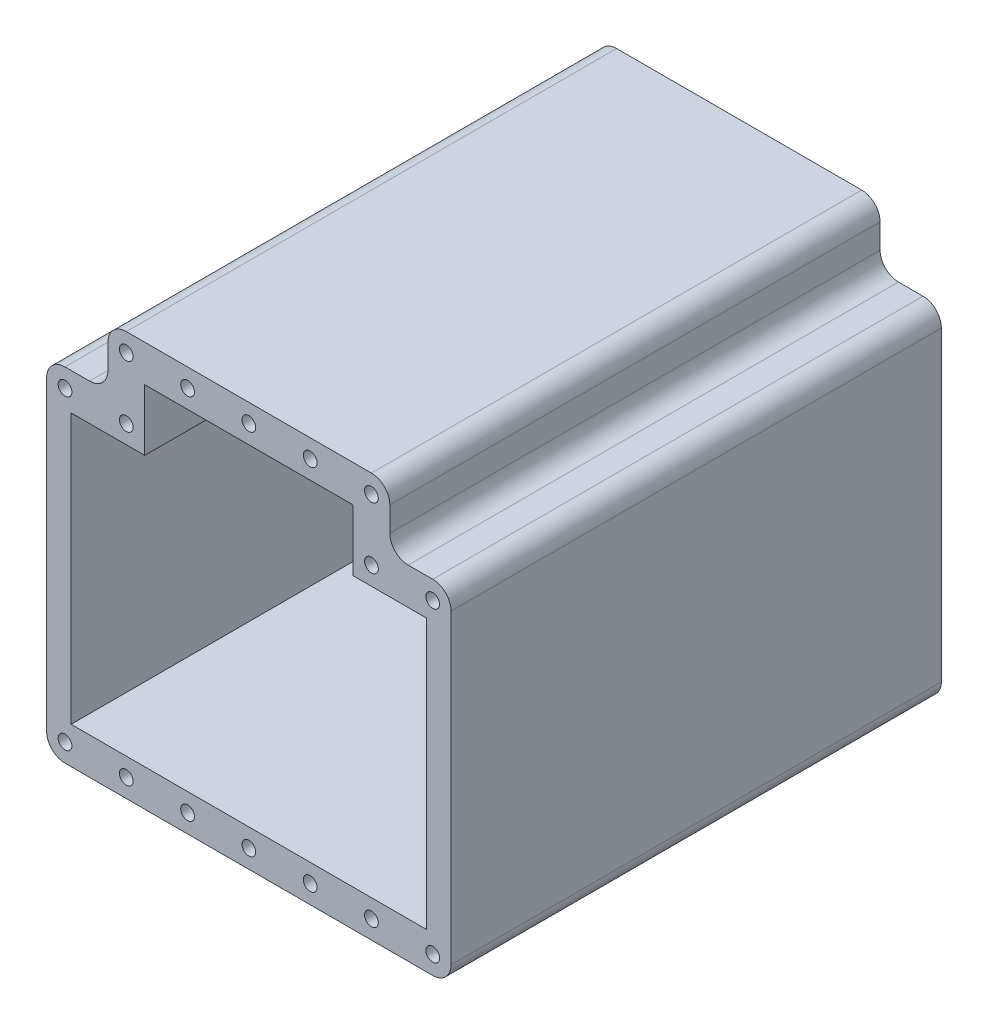
SolidWorks part; units mm, degrees
ref_plane "Front Plane" through (0, 0, 0) normal (0, 0, 1) x (1, 0, 0)
ref_plane "Top Plane" through (0, 0, 0) normal (0, 1, 0) x (1, 0, 0)
ref_plane "Right Plane" through (0, 0, 0) normal (1, 0, 0) x (0, 0, -1)
sketch "Sketch2" plane through (0, 0, 0) normal (0, 0, 1) x (1, 0, 0)
  line L5 (-57.5, 60) -> (-57.5, 50)
  line L6 (-75, -97.5) -> (75, -97.5)
  line L24 (-82.5, -90) -> (-82.5, 35)
  line L25 (-50, 67.5) -> (50, 67.5)
  line L26 (82.5, -90) -> (82.5, 35)
  line L27 (0, -100) -> (0, 100) construction
  line L28 (-100, 0) -> (100, 0) construction
  line L29 (-65, 42.5) -> (-75, 42.5)
  line L34 (57.5, 60) -> (57.5, 50)
  line L35 (65, 42.5) -> (75, 42.5)
  arc A12 (-82.5, 35) -> (-75, 42.5) centre (-75, 35) cw
  arc A19 (82.5, 35) -> (75, 42.5) centre (75, 35) ccw
  arc A20 (65, 42.5) -> (57.5, 50) centre (65, 50) cw
  arc A21 (57.5, 60) -> (50, 67.5) centre (50, 60) ccw
  arc A22 (-50, 67.5) -> (-57.5, 60) centre (-50, 60) ccw
  arc A23 (-65, 42.5) -> (-57.5, 50) centre (-65, 50) ccw
  arc A24 (-82.5, -90) -> (-75, -97.5) centre (-75, -90) ccw
  arc A25 (82.5, -90) -> (75, -97.5) centre (75, -90) cw
  point P0 (0, 0)
  point P39 (-57.5, 67.5)
  dimension "D5" = 25
  dimension "D6" = 82.5
  dimension "D7" = 7.5
  dimension "D2" = 25
  dimension "D3" = 165
  dimension "D8" = 7.5
  dimension "D1" = 67.5
  dimension "D4" = 82.5
extrude "Boss-Extrude1" add sketch "Sketch2" against normal blind 200
sketch "Sketch8" plane through (0, 0, 0) normal (0, 0, 1) x (1, 0, 0)
  line L0 (-72.5, 27.5) -> (-42.5, 27.5)
  line L1 (-42.5, 27.5) -> (-42.5, 52.5)
  line L2 (-42.5, 52.5) -> (42.5, 52.5)
  line L3 (42.5, 52.5) -> (42.5, 27.5)
  line L4 (42.5, 27.5) -> (72.5, 27.5)
  line L5 (72.5, 27.5) -> (72.5, -82.5)
  line L6 (72.5, -82.5) -> (-72.5, -82.5)
  line L7 (-72.5, -82.5) -> (-72.5, 27.5)
  line L8 (-65, 42.5) -> (-75, 42.5) construction
  line L9 (-82.5, 35) -> (-82.5, -90) construction
  line L10 (-57.5, 60) -> (-57.5, 50) construction
  line L11 (50, 67.5) -> (-50, 67.5) construction
  line L12 (57.5, 50) -> (57.5, 60) construction
  line L13 (75, 42.5) -> (65, 42.5) construction
  line L14 (82.5, -90) -> (82.5, 35) construction
  line L15 (-75, -97.5) -> (75, -97.5) construction
  dimension "D1" = 15
  dimension "D2" = 10
  dimension "D3" = 15
  dimension "D4" = 15
  dimension "D5" = 15
  dimension "D6" = 15
  dimension "D7" = 10
  dimension "D8" = 15
extrude "Cut-Extrude2" cut sketch "Sketch8" against normal through all both and the other way through all
sketch "Sketch10" plane through (0, 0, 0) normal (0, 0, 1) x (1, 0, 0)
  line L0 (-75, 35) -> (-50, 35) construction
  line L1 (-50, 35) -> (-50, 60) construction
  line L2 (-50, 60) -> (50, 60) construction
  line L3 (-42.5, 27.5) -> (-42.5, 52.5) construction
  line L4 (50, 35) -> (50, 60) construction
  line L5 (50, 35) -> (75, 35) construction
  line L7 (-42.5, 52.5) -> (42.5, 52.5) construction
  line L9 (-75, -90) -> (75, -90) construction
  arc A0 (-82.5, -90) -> (-75, -97.5) centre (-75, -90) ccw construction
  arc A1 (-82.5, -90) -> (-75, -97.5) centre (-75, -90) ccw construction
  arc A2 (75, -97.5) -> (82.5, -90) centre (75, -90) ccw construction
  point P13 (-25, 60)
  point P14 (-75, 35)
  point P15 (-50, 35)
  point P16 (-50, 60)
  point P17 (50, 60)
  point P18 (50, 35)
  point P19 (75, 35)
  point P20 (0, 60)
  point P21 (25, 60)
  point P32 (-75, -90)
  point P36 (-50, -90)
  point P37 (-25, -90)
  point P38 (0, -90)
  point P39 (25, -90)
  point P40 (50, -90)
  point P41 (75, -90)
  dimension "D1" = 7.5
  dimension "D2" = 7.5
  dimension "D3" = 25
  dimension "D4" = 25
  dimension "D5" = 25
  dimension "D6" = 25
  dimension "D8" = 7
hole_wizard "Ø1.0mm Dowel Hole2" positions "Sketch10" profile "Sketch11" hole size "Ø1.0" standard "ANSI Metric" end condition through all
sketch "Sketch11" plane through (75, -90, 0) normal (1, 0, 0) x (0, -1, 0)
  line L0 (0, 0) -> (0, 200)
  line L1 (0, 200) -> (2.8, 200)
  line L2 (2.8, 200) -> (2.8, 0)
  line L5 (2.8, 0) -> (0, 0)
  line L11 (0, -6.35) -> (0, 107.95) construction
  dimension "Thru Hole Dia." = 5.6
  dimension "Thru Hole Depth" = 200
